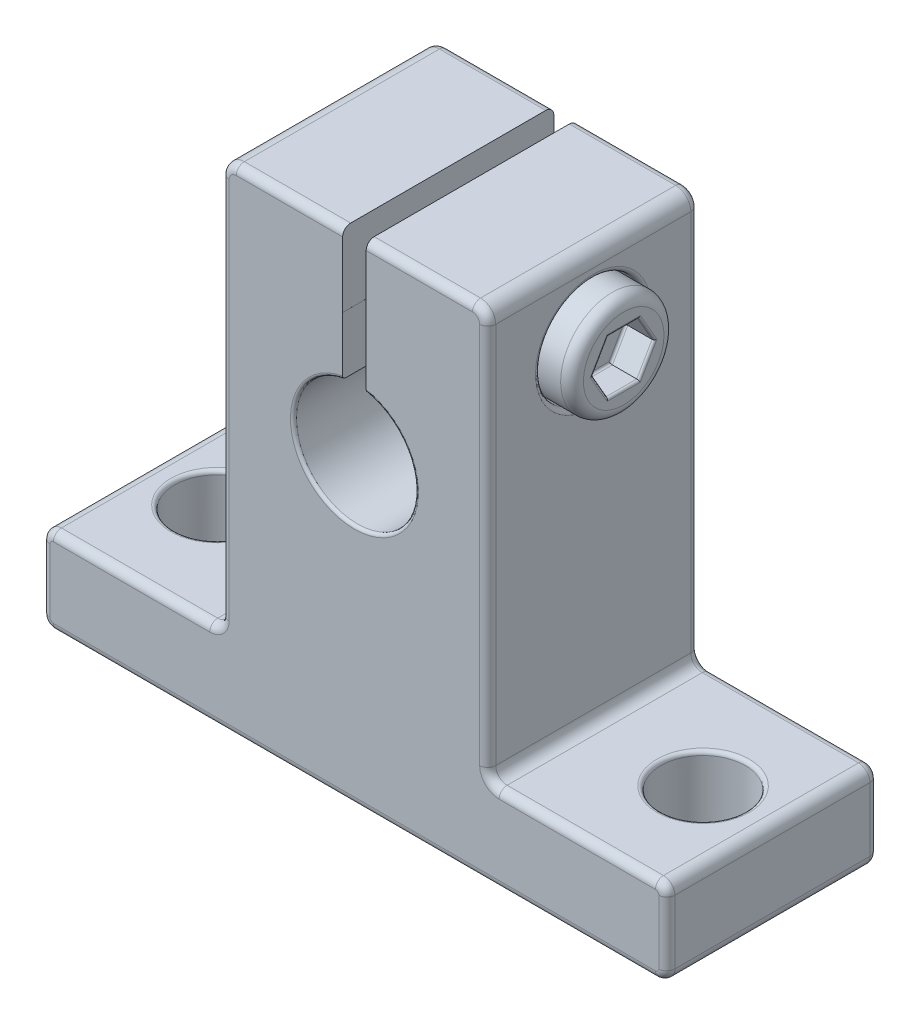
SolidWorks part; units mm, degrees
ref_plane "Plano frontal" through (0, 0, 0) normal (0, 0, 1) x (1, 0, 0)
ref_plane "Plano superior" through (0, 0, 0) normal (0, 1, 0) x (1, 0, 0)
ref_plane "Plano direito" through (0, 0, 0) normal (1, 0, 0) x (0, 0, -1)
sketch "Esboço1" plane through (0, 0, 0) normal (0, 0, 1) x (1, 0, 0)
  line L0 (-7.7757, 16.3) -> (-0.7757, 16.3)
  line L1 (-19.815, -16.3) -> (19.815, -16.3)
  line L2 (-20.565, -15.55) -> (-20.565, -11.35)
  line L3 (-19.815, -10.6) -> (-9.5257, -10.6)
  line L4 (20.565, -15.55) -> (20.565, -11.35)
  line L5 (0.7743, 16.3) -> (7.7743, 16.3)
  line L6 (9.5243, -10.6) -> (19.815, -10.6)
  line L7 (8.7743, 15.3) -> (8.7743, -9.85)
  line L8 (-8.7757, 15.3) -> (-8.7757, -9.85)
  line L10 (-0.7757, 11.4644) -> (-0.7757, 16.3)
  line L12 (0.7743, 11.4644) -> (0.7743, 16.3)
  arc A0 (8.7743, 15.3) -> (7.7743, 16.3) centre (7.7743, 15.3) ccw
  arc A1 (-7.7757, 16.3) -> (-8.7757, 15.3) centre (-7.7757, 15.3) ccw
  arc A2 (-20.565, -15.55) -> (-19.815, -16.3) centre (-19.815, -15.55) ccw
  arc A3 (-20.565, -11.35) -> (-19.815, -10.6) centre (-19.815, -11.35) cw
  arc A4 (19.815, -10.6) -> (20.565, -11.35) centre (19.815, -11.35) cw
  arc A5 (19.815, -16.3) -> (20.565, -15.55) centre (19.815, -15.55) ccw
  arc A6 (8.7743, -9.85) -> (9.5243, -10.6) centre (9.5243, -9.85) ccw
  arc A7 (-8.7757, -9.85) -> (-9.5257, -10.6) centre (-9.5257, -9.85) cw
  arc A8 (-0.7757, 11.4644) -> (0.7743, 11.4644) centre (-0.0007, 7.53) ccw
  point P0 (0, 0)
  point P9 (8.7743, 16.3)
  point P15 (-8.7757, 16.3)
  point P18 (-20.565, -16.3)
  point P23 (20.565, -10.6)
  point P26 (20.565, -16.3)
  point P29 (8.7743, -10.6)
  dimension "D1" = 1
  dimension "D4" = 0.75
  dimension "D6" = 8.02
  dimension "D2" = 41.13
  dimension "D3" = 17.55
  dimension "D5" = 5.7
extrude "Ressalto-extrusão1" add sketch "Esboço1" along normal blind 13.9
fillet "Filete2" radius 0.53 34 edges at (-4.2757, 16.3, 13.9) (-8.4828, 16.0071, 13.9) (4.2743, 16.3, 13.9) (8.4814, 16.0071, 13.9) (8.7743, 2.725, 13.9) (8.994, -10.3803, 13.9) (14.6697, -10.6, 13.9) (20.3453, -10.8197, 13.9) (20.565, -13.45, 13.9) (20.3453, -16.0803, 13.9) (0, -16.3, 13.9) (-20.3453, -16.0803, 13.9) (-20.565, -13.45, 13.9) (-20.3453, -10.8197, 13.9) (-14.6703, -10.6, 13.9) (-8.9954, -10.3803, 13.9) (-4.2757, 16.3, 0) (-8.4828, 16.0071, 0) (4.2743, 16.3, 0) (8.4814, 16.0071, 0) (8.7743, 2.725, 0) (8.994, -10.3803, 0) (14.6697, -10.6, 0) (20.3453, -10.8197, 0) (20.565, -13.45, 0) (20.3453, -16.0803, 0) (0, -16.3, 0) (-20.3453, -16.0803, 0) (-20.565, -13.45, 0) (-20.3453, -10.8197, 0) (-14.6703, -10.6, 0) (-8.9954, -10.3803, 0) (-8.7757, 2.725, 13.9) (-8.7757, 2.725, 0)
sketch "Esboço9" plane through (0, 0, 0) normal (0, 0, -1) x (-1, 0, 0)
  circle A1 centre (0.0007, 7.53) radius 4.01
extrude "Ressalto-extrusão4" add sketch "Esboço9" against normal blind 13.9
sketch "Esboço10" plane through (0, 0, 13.9) normal (0, 0, 1) x (1, 0, 0)
  line L0 (-0.7743, 16.3) -> (-0.7743, 7.6445)
  line L1 (0.7743, 11.4644) -> (0.7743, 7.6445)
  line L3 (-0.7743, 16.3) -> (0.7743, 16.3)
  line L4 (0.7743, 11.4644) -> (0.7743, 16.3)
  line L5 (0.7743, 11.4644) -> (0.7743, 16.3)
  line L8 (0.7743, 11.4644) -> (0.7743, 16.3)
  arc A0 (-0.7743, 7.6445) -> (0.7743, 7.6445) centre (0, 3.71) ccw
  dimension "D1" = 8.02
extrude "Corte-extrusão8" cut sketch "Esboço10" against normal blind 20.9 and the other way blind 16 contours L0 A0 L1 | L4 L3 L0 region at (0, 5.4398, 13.9)
fillet "Filete12" radius 0.2 1 edges at (0, -0.3, 0)
fillet "Filete13" radius 0.2 1 edges at (0, -0.3, 13.9)
sketch "Esboço14" plane through (-8.7757, 0, 0) normal (-1, 0, 0) x (0, 0, 1)
  circle A0 centre (6.95, 11.144) radius 1.71
  dimension "D1" = 3.42
extrude "Corte-extrusão9" cut sketch "Esboço14" against normal blind 20.9
fillet "Filete14" radius 0.2 1 edges at (-8.7757, 9.434, 6.95)
sketch "Esboço15" plane through (8.7743, 0, 0) normal (1, 0, 0) x (0, 0, -1)
  circle A0 centre (-6.95, 11.144) radius 3.5
  dimension "D1" = 7
extrude "Corte-extrusão10" cut sketch "Esboço15" against normal blind 3.9
fillet "Filete16" radius 0.3 1 edges at (8.7743, 14.644, 6.95)
sketch "Esboço16" plane through (4.8743, 0, 0) normal (1, 0, 0) x (0, 0, -1)
  circle A0 centre (-6.95, 11.144) radius 3.4
  dimension "D1" = 6.8
extrude "Ressalto-extrusão5" add sketch "Esboço16" along normal blind 5.9
fillet "Filete19" radius 0.75 2 edges at (4.8743, 14.544, 6.95) (10.7743, 14.544, 6.95)
sketch "Esboço17" plane through (10.7743, 0, 0) normal (1, 0, 0) x (0, 0, -1)
  line L1 (-4.9293, 11.144) -> (-5.9396, 12.894)
  line L2 (-5.9396, 12.894) -> (-7.9604, 12.894)
  line L3 (-7.9604, 12.894) -> (-8.9707, 11.144)
  line L4 (-8.9707, 11.144) -> (-7.9604, 9.394)
  line L5 (-7.9604, 9.394) -> (-5.9396, 9.394)
  line L6 (-5.9396, 9.394) -> (-4.9293, 11.144)
  circle A0 centre (-6.95, 11.144) radius 1.75 construction
  point P1 (-6.95, 9.394)
  dimension "D1" = 3.5
extrude "Corte-extrusão11" cut sketch "Esboço17" against normal blind 1.9
fillet "Filete20" radius 0.15 12 edges at (10.7743, 12.019, 5.4345) (10.7743, 12.894, 6.95) (10.7743, 12.019, 8.4655) (10.7743, 10.269, 8.4655) (10.7743, 9.394, 6.95) (10.7743, 10.269, 5.4345) (8.8743, 9.394, 6.95) (8.8743, 10.269, 8.4655) (8.8743, 12.019, 8.4655) (8.8743, 12.894, 6.95) (8.8743, 12.019, 5.4345) (8.8743, 10.269, 5.4345)
sketch "Esboço18" plane through (4.8743, 0, 0) normal (-1, 0, 0) x (0, 0, 1)
  circle A0 centre (6.95, 11.144) radius 1.7
  dimension "D1" = 3.4
extrude "Ressalto-extrusão6" add sketch "Esboço18" along normal blind 12.9
sketch "Esboço19" plane through (0, -16.3, 0) normal (0, -1, 0) x (1, 0, 0)
  circle A0 centre (-16, 6.95) radius 2.79
  circle A1 centre (16, 6.95) radius 2.79
  dimension "D2" = 5.58
  dimension "D3" = 5.58
  dimension "D1" = 32
extrude "Corte-extrusão12" cut sketch "Esboço19" along normal blind 7.9 and the other way blind 17
fillet "Filete21" radius 0.25 1 edges at (18.79, -10.6, 6.95)
fillet "Filete22" radius 0.25 3 edges at (-16, -16.3, 9.74) (16, -16.3, 9.74) (-16, -10.6, 4.16)
